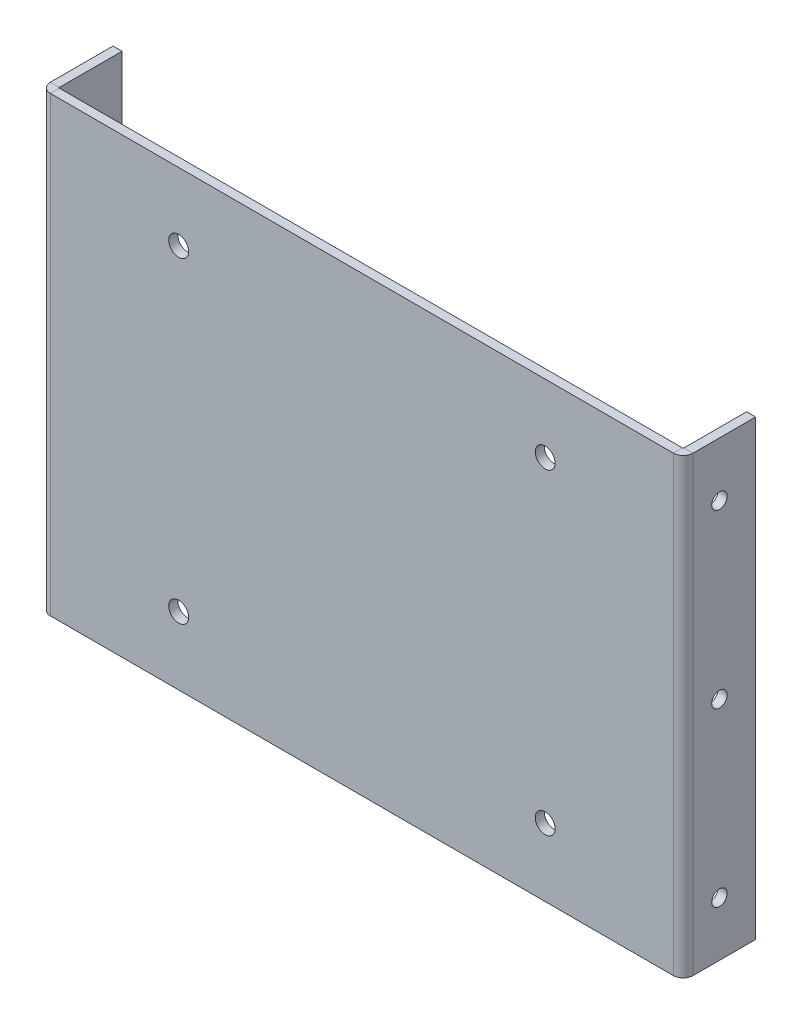
SolidWorks part; units mm, degrees
note: The reader was unsure of these and kept them because the rebuilt part matched: flange length of "Edge-Flange1", "Edge-Flange2".
material "1023 Carbon Steel Sheet (SS)"
ref_plane "Front Plane" through (0, 0, 0) normal (0, 0, 1) x (1, 0, 0)
ref_plane "Top Plane" through (0, 0, 0) normal (0, 1, 0) x (1, 0, 0)
ref_plane "Right Plane" through (0, 0, 0) normal (1, 0, 0) x (0, 0, -1)
sketch "Sketch1" plane through (0, 0, 0) normal (0, 0, 1) x (1, 0, 0)
  line L1 (-355, -250) -> (355, -250)
  line L2 (-355, -250) -> (-355, 250)
  line L3 (-355, 250) -> (355, 250)
  line L4 (355, -250) -> (355, 250)
  line L5 (-355, -250) -> (355, 250) construction
  line L6 (-355, 250) -> (355, -250) construction
  point P0 (0, 0)
  dimension "D1" = 710
  dimension "D2" = 500
base flange "Base-Flange1" sketch "Sketch1" thickness 10 reverse thickness direction no parameters "D1"=0.7366
edge flange "Edge-Flange1" sketch "Sketch8" flange angle 90 flange length 80 flange position material inside bend radius 0.7366 thickness 10 relief rectangular parameters "D6"=10
sketch "Sketch8" plane through (-355, 0, -10) normal (1, 0, 0) x (0, -1, 0)
  line L1 (250, 0) -> (-250, 0) construction
  line L2 (-250, 0) -> (-250, 70)
  line L3 (-250, 70) -> (250, 70)
  line L4 (250, 70) -> (250, 0)
  line L5 (250, 0) -> (-250, 0)
bend "EdgeBend1" bend radius 0.7366 bend angle 90 parameters "D5"=1
edge flange "Edge-Flange2" sketch "Sketch11" flange angle 90 flange length 80 flange position material inside bend radius 0.7366 thickness 10 relief rectangular parameters "D6"=10
sketch "Sketch11" plane through (355, 0, -10) normal (-1, 0, 0) x (0, 1, 0)
  line L1 (250, 0) -> (-250, 0) construction
  line L2 (-250, 0) -> (-250, 70)
  line L3 (-250, 70) -> (250, 70)
  line L4 (250, 70) -> (250, 0)
  line L5 (250, 0) -> (-250, 0)
bend "EdgeBend2" bend radius 0.7366 bend angle 90 parameters "D5"=2
sketch "Sketch12" plane through (-355, 0, 0) normal (-1, 0, 0) x (0, 0, 1)
  line L0 (-80, -250) -> (-80, 250) construction
  line L1 (-80, 250) -> (-10.7366, 250) construction
  circle A0 centre (-40, 190) radius 8.5
  dimension "D1" = 17
  dimension "D2" = 40
  dimension "D3" = 60
extrude "Cut-Extrude1" cut sketch "Sketch12" against normal through all both and the other way through all normal cut yes
pattern_linear "LPattern1" count 3 spacing 190 along (0, -1, 0) of "Cut-Extrude1"
sketch "Sketch13" plane through (0, 0, 0) normal (0, 0, 1) x (1, 0, 0)
  circle A0 centre (202.5, 175) radius 11
  point P0 (0, 0)
  dimension "D3" = 22
extrude "Cut-Extrude2" cut sketch "Sketch13" against normal through all both and the other way through all normal cut yes
pattern_linear "LPattern2" count 2 spacing 405 along (-1, 0, 0) count 2 spacing 350 along (0, -1, 0) of "Cut-Extrude2"
sketch "Bend-Lines1" [suppressed] plane through (0, 0, 0) normal (0, 1, 0) x (1, 0, 0)
sketch "Bounding-Box1" [suppressed] plane through (0, 0, 0) normal (0, 1, 0) x (1, 0, 0)
sheet metal parameters "Sheet-Metal1" thickness 10 parameters "D1"=0.7366
flat pattern "Flat-Pattern1" [suppressed]
sketch "Bend-Lines2" plane through (0, 0, 0) normal (0, 1, 0) x (1, 0, 0)
sketch3d "Bounding-Box2" [suppressed]
  line L0 (355, -250, 0) -> (-355, -250, 0) construction
  line L1 (355, 250, 0) -> (-355, 250, 0) construction
  line L2 (355, -250, 0) -> (355, 250, 0) construction
  line L3 (-355, -250, 0) -> (-355, 250, 0) construction
sheet metal parameters "Sheet-Metal2" thickness 10 parameters "D1"=0.7366
flat pattern "Flat-Pattern1"
sketch "Bend-Lines2" plane through (0, 0, 0) normal (0, 0, 1) x (1, 0, 0)
  line L0 (-348.7689, 250) -> (-348.7689, -250) construction
  line L1 (-348.7689, 250) -> (-348.7689, -250) construction
sketch3d "Bounding-Box2" [suppressed]
  line L0 (-422.5378, -250, 0) -> (355, -250, 0) construction
  line L1 (-422.5378, 250, 0) -> (355, 250, 0) construction
  line L2 (-422.5378, -250, 0) -> (-422.5378, 250, 0) construction
  line L3 (355, -250, 0) -> (355, 250, 0) construction
bend of the flat pattern "Flatten-<EdgeBend1>1"
sheet metal parameters "Sheet-Metal3" thickness 10 parameters "D1"=0.7366
flat pattern "Flat-Pattern1"
sketch "Bend-Lines2" plane through (0, 0, 0) normal (0, 0, 1) x (1, 0, 0)
  line L0 (-348.7689, 250) -> (-348.7689, -250) construction
  line L1 (-348.7689, 250) -> (-348.7689, -250) construction
  line L2 (348.7689, -250) -> (348.7689, 250) construction
  line L3 (348.7689, -250) -> (348.7689, 250) construction
sketch3d "Bounding-Box2" [suppressed]
  line L0 (-422.5378, -250, 0) -> (422.5378, -250, 0) construction
  line L1 (-422.5378, 250, 0) -> (422.5378, 250, 0) construction
  line L2 (-422.5378, -250, 0) -> (-422.5378, 250, 0) construction
  line L3 (422.5378, -250, 0) -> (422.5378, 250, 0) construction
bend of the flat pattern "Flatten-<EdgeBend1>1"
bend of the flat pattern "Flatten-<EdgeBend2>1"
sheet metal parameters "Sheet-Metal4" thickness 10 parameters "D1"=0.7366
flat pattern "Flat-Pattern1"
sketch "Bend-Lines2" plane through (0, 0, 0) normal (0, 0, 1) x (1, 0, 0)
  line L0 (-348.7689, 250) -> (-348.7689, -250) construction
  line L1 (-348.7689, 250) -> (-348.7689, -250) construction
  line L2 (348.7689, -250) -> (348.7689, 250) construction
  line L3 (348.7689, -250) -> (348.7689, 250) construction
sketch3d "Bounding-Box2" [suppressed]
  line L0 (-422.5378, -250, 0) -> (422.5378, -250, 0) construction
  line L1 (-422.5378, 250, 0) -> (422.5378, 250, 0) construction
  line L2 (-422.5378, -250, 0) -> (-422.5378, 250, 0) construction
  line L3 (422.5378, -250, 0) -> (422.5378, 250, 0) construction
bend of the flat pattern "Flatten-<EdgeBend1>1"
bend of the flat pattern "Flatten-<EdgeBend2>1"
sheet metal parameters "Sheet-Metal5" thickness 10 parameters "D1"=0.7366
flat pattern "Flat-Pattern1"
sketch "Bend-Lines2" plane through (0, 0, 0) normal (0, 0, 1) x (1, 0, 0)
  line L0 (-348.7689, 250) -> (-348.7689, -250) construction
  line L1 (-348.7689, 250) -> (-348.7689, -250) construction
  line L2 (348.7689, -250) -> (348.7689, 250) construction
  line L3 (348.7689, -250) -> (348.7689, 250) construction
sketch3d "Bounding-Box2" [suppressed]
  line L0 (-422.5378, -250, 0) -> (422.5378, -250, 0) construction
  line L1 (-422.5378, 250, 0) -> (422.5378, 250, 0) construction
  line L2 (-422.5378, -250, 0) -> (-422.5378, 250, 0) construction
  line L3 (422.5378, -250, 0) -> (422.5378, 250, 0) construction
bend of the flat pattern "Flatten-<EdgeBend1>1"
bend of the flat pattern "Flatten-<EdgeBend2>1"
sheet metal parameters "Sheet-Metal6" thickness 10 parameters "D1"=0.7366
flat pattern "Flat-Pattern1"
sketch "Bend-Lines2" plane through (0, 0, 0) normal (0, 0, 1) x (1, 0, 0)
  line L0 (-348.7689, 250) -> (-348.7689, -250) construction
  line L1 (-348.7689, 250) -> (-348.7689, -250) construction
  line L2 (348.7689, -250) -> (348.7689, 250) construction
  line L3 (348.7689, -250) -> (348.7689, 250) construction
sketch3d "Bounding-Box2" [suppressed]
  line L0 (-422.5378, -250, 0) -> (422.5378, -250, 0) construction
  line L1 (-422.5378, 250, 0) -> (422.5378, 250, 0) construction
  line L2 (-422.5378, -250, 0) -> (-422.5378, 250, 0) construction
  line L3 (422.5378, -250, 0) -> (422.5378, 250, 0) construction
bend of the flat pattern "Flatten-<EdgeBend1>1"
bend of the flat pattern "Flatten-<EdgeBend2>1"
sheet metal parameters "Sheet-Metal7" thickness 10 parameters "D1"=0.7366
flat pattern "Flat-Pattern1"
sketch "Bend-Lines2" plane through (0, 0, 0) normal (0, 0, 1) x (1, 0, 0)
  line L0 (-348.7689, 250) -> (-348.7689, -250) construction
  line L1 (-348.7689, 250) -> (-348.7689, -250) construction
  line L2 (348.7689, -250) -> (348.7689, 250) construction
  line L3 (348.7689, -250) -> (348.7689, 250) construction
sketch3d "Bounding-Box2" [suppressed]
  line L0 (-422.5378, -250, 0) -> (422.5378, -250, 0) construction
  line L1 (-422.5378, 250, 0) -> (422.5378, 250, 0) construction
  line L2 (-422.5378, -250, 0) -> (-422.5378, 250, 0) construction
  line L3 (422.5378, -250, 0) -> (422.5378, 250, 0) construction
bend of the flat pattern "Flatten-<EdgeBend1>1"
bend of the flat pattern "Flatten-<EdgeBend2>1"
